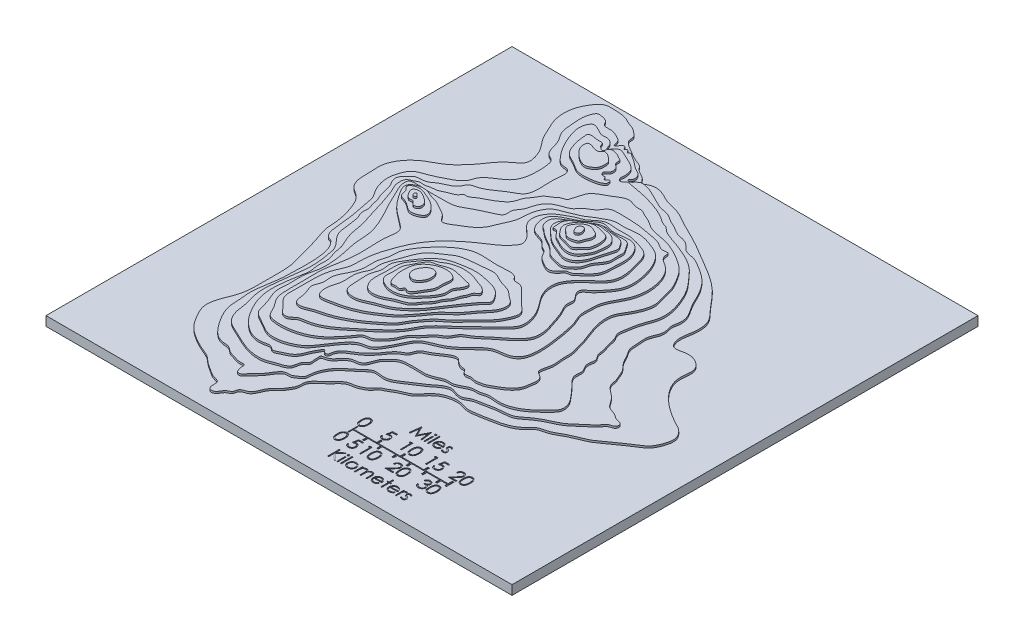
SolidWorks part; units mm, degrees
ref_plane "Front Plane" through (0, 0, 0) normal (0, 0, 1) x (1, 0, 0)
ref_plane "Top Plane" through (0, 0, 0) normal (0, 1, 0) x (1, 0, 0)
ref_plane "Right Plane" through (0, 0, 0) normal (1, 0, 0) x (0, 0, -1)
sketch "Sketch1" plane through (0, 0, 0) normal (0, 1, 0) x (1, 0, 0)
  line L1 (-63.5, -63.5) -> (63.5, -63.5)
  line L2 (-63.5, -63.5) -> (-63.5, 63.5)
  line L3 (-63.5, 63.5) -> (63.5, 63.5)
  line L4 (63.5, -63.5) -> (63.5, 63.5)
  line L5 (-63.5, -63.5) -> (63.5, 63.5) construction
  line L6 (-63.5, 63.5) -> (63.5, -63.5) construction
  point P0 (0, 0)
  dimension "D1" = 127
  dimension "D2" = 127
extrude "Table" add sketch "Sketch1" along normal blind 2.54
sketch "Master" plane through (0, 2.54, 0) normal (0, 1, 0) x (1, 0, 0)
  line L0 (28.8333, 259.5) -> (398.1667, 259.5) construction
  line L1 (6.35, -46.8068) -> (29.21, -46.8068) construction
  line L2 (5.0423, -48.3753) -> (31.4087, -48.3753)
  line L3 (5.0423, -48.3753) -> (5.0423, -48.6293)
  line L4 (5.0423, -48.6293) -> (31.4087, -48.6293)
  line L5 (31.4087, -48.3753) -> (31.4087, -48.6293)
  line L6 (30.9502, -47.2308) -> (31.4087, -47.2308)
  line L7 (30.9502, -47.2308) -> (30.9502, -49.2894)
  line L8 (30.9502, -49.2894) -> (31.4087, -49.2894)
  line L9 (31.4087, -47.2308) -> (31.4087, -49.2894)
  line L10 (28.8818, -48.6293) -> (29.3366, -48.6293)
  line L11 (28.8818, -48.6293) -> (28.8818, -49.7264)
  line L12 (28.8818, -49.7264) -> (29.3366, -49.7264)
  line L13 (29.3366, -48.6293) -> (29.3366, -49.7264)
  line L14 (24.9746, -48.6293) -> (25.4571, -48.6293)
  line L15 (24.9746, -48.6293) -> (24.9746, -49.7264)
  line L16 (24.9746, -49.7264) -> (25.4571, -49.7264)
  line L17 (25.4571, -48.6293) -> (25.4571, -49.7264)
  line L18 (24.3147, -47.2308) -> (24.7619, -47.2308)
  line L19 (24.3147, -47.2308) -> (24.3147, -48.3753)
  line L20 (24.3147, -48.3753) -> (24.7619, -48.3753)
  line L21 (24.7619, -47.2308) -> (24.7619, -48.3753)
  line L22 (20.8599, -48.6293) -> (21.3202, -48.6293)
  line L23 (20.8599, -48.6293) -> (20.8599, -49.7264)
  line L24 (20.8599, -49.7264) -> (21.3202, -49.7264)
  line L25 (21.3202, -48.6293) -> (21.3202, -49.7264)
  line L26 (16.9577, -48.6293) -> (17.4289, -48.6293)
  line L27 (16.9577, -48.6293) -> (16.9577, -49.7264)
  line L28 (16.9577, -49.7264) -> (17.4289, -49.7264)
  line L29 (17.4289, -48.6293) -> (17.4289, -49.7264)
  line L30 (17.8871, -47.2308) -> (18.3452, -47.2308)
  line L31 (17.8871, -47.2308) -> (17.8871, -48.3753)
  line L32 (17.8871, -48.3753) -> (18.3452, -48.3753)
  line L33 (18.3452, -47.2308) -> (18.3452, -48.3753)
  line L34 (12.843, -48.6293) -> (13.292, -48.6293)
  line L35 (12.843, -48.6293) -> (12.843, -49.7264)
  line L36 (12.843, -49.7264) -> (13.292, -49.7264)
  line L37 (13.292, -48.6293) -> (13.292, -49.7264)
  line L38 (11.476, -47.2308) -> (11.9251, -47.2308)
  line L39 (11.476, -47.2308) -> (11.476, -48.3753)
  line L40 (11.476, -48.3753) -> (11.9251, -48.3753)
  line L41 (11.9251, -47.2308) -> (11.9251, -48.3753)
  line L42 (8.9486, -48.6293) -> (9.3972, -48.6293)
  line L43 (8.9486, -48.6293) -> (8.9486, -49.7264)
  line L44 (8.9486, -49.7264) -> (9.3972, -49.7264)
  line L45 (9.3972, -48.6293) -> (9.3972, -49.7264)
  line L46 (5.0423, -48.3753) -> (5.2588, -48.3753)
  line L47 (5.0423, -48.3753) -> (5.0423, -47.2308)
  line L48 (5.0423, -47.2308) -> (5.2588, -47.2308)
  line L49 (5.2588, -48.3753) -> (5.2588, -47.2308)
  line L50 (5.0423, -48.6293) -> (5.2588, -48.6293)
  line L51 (5.0423, -48.6293) -> (5.0423, -49.7264)
  line L52 (5.0423, -49.7264) -> (5.2588, -49.7264)
  line L53 (5.2588, -48.6293) -> (5.2588, -49.7264)
  line L54 (13.292, -41.6326) -> (23.4459, -41.6326) construction
  line L55 (23.4459, -41.6326) -> (23.4459, -46.8068) construction
  line L56 (23.4459, -46.8068) -> (23.4459, -48.3753) construction
  line L57 (6.35, -53.34) -> (26.67, -53.3257) construction
  line L58 (26.67, -53.3257) -> (26.67, -58.2919) construction
  line L59 (26.67, -58.2919) -> (7.62, -58.2919) construction
  line L60 (22.5347, -48.6293) -> (22.5347, -53.3286) construction
  spline S0 degree 3 number of poles 136 (-30.2533, 61.4196) -> (-30.2533, 61.4196)
  spline S1 degree 3 number of poles 164 (-35.5805, 57.4705) -> (-35.5805, 57.4705)
  spline S2 degree 3 number of poles 140 (-33.4819, 53.3721) -> (-33.4819, 53.3721)
  spline S3 degree 3 poles (-26.25, 51.1954) (-27.5323, 51.0076) (-28.575, 51.2687) (-30.6963, 51.4713) (-30.3649, 49.7693) (-30.3171, 48.3479) (-29.7101, 46.1998) (-28.5554, 43.5195) (-25.7194, 42.6435) (-23.1147, 40.5022) (-19.8391, 40.7603) (-17.3898, 41.1982) (-16.1906, 42.0292) (-16.2154, 42.7209) (-16.5264, 43.7067) (-17.4633, 42.1742) (-17.7597, 43.0865) (-18.0522, 43.4981) (-18.5561, 43.2978) (-19.0607, 43.5182) (-19.4986, 43.9714) (-19.2974, 44.55) (-18.9531, 44.9092) (-18.1361, 45.4421) (-18.3728, 46.8498) (-19.1699, 47.4741) (-19.6627, 47.8231) (-19.9632, 48.4852) (-19.6996, 49.4175) (-20.808, 49.7315) (-21.5934, 50.4228) (-22.6702, 50.6189) (-23.6199, 50.7926) (-24.2289, 50.2669) (-24.2639, 49.7102) (-24.6735, 49.0969) (-25.3781, 49.6079) (-26.0745, 50.0605) (-26.25, 51.1954) (-27.5323, 51.0076) (-28.575, 51.2687) knots -0.055235 -0.036483 -0.009705 0 0.043313 0.079211 0.100968 0.139976 0.183739 0.251086 0.32677 0.373438 0.477244 0.527201 0.552559 0.56082 0.575588 0.601018 0.616226 0.621801 0.633895 0.645623 0.65892 0.671786 0.682091 0.693251 0.736089 0.74848 0.76343 0.776187 0.796472 0.816749 0.840821 0.869342 0.889931 0.902722 0.918216 0.92825 0.944765 0.963517 0.990295 1 1.043313 1.079211 1.100968 only from (-26.9845, 51.0961) to (-26.9845, 51.0961)
  spline S4 degree 3 poles (-23.8681, 48.8647) (-24.2474, 47.8693) (-25.5025, 47.9527) (-26.4325, 48.42) (-27.9645, 48.7604) (-28.1074, 47.5041) (-27.9803, 46.5295) (-27.0766, 45.2128) (-25.8718, 44.0711) (-24.3589, 43.1337) (-22.9884, 42.6671) (-21.9283, 43.1795) (-21.159, 43.6249) (-20.541, 44.453) (-20.4464, 45.6175) (-20.4924, 47.0156) (-21.4827, 47.7844) (-22.2461, 48.44) (-22.9571, 48.7456) (-23.8681, 48.8647) (-24.2474, 47.8693) (-25.5025, 47.9527) knots -0.11115 -0.071618 -0.042286 0 0.043927 0.10396 0.164652 0.19766 0.251336 0.30265 0.41016 0.476707 0.549357 0.592242 0.632479 0.671219 0.727506 0.790535 0.850099 0.88885 0.928382 0.957714 1 1.043927 1.10396 1.164652 only from (-24.3519, 48.0739) to (-24.3519, 48.0739)
  spline S5 degree 3 number of poles 122 (-30.9511, 20.7382) -> (-30.9511, 20.7382)
  spline S6 degree 3 number of poles 74 (-43.2944, 15.0999) -> (-43.2944, 15.0999)
  spline S7 degree 3 number of poles 71 (-42.0642, 13.5601) -> (-42.0642, 13.5601)
  spline S8 degree 3 poles (-37.2309, 13.4684) (-39.7598, 14.4094) (-41.8012, 12.5919) (-40.0411, 11.562) (-40.3673, 9.5716) (-38.3217, 9.1819) (-36.8913, 8.3368) (-35.4914, 7.0475) (-33.5219, 7.1297) (-31.3018, 8.3047) (-32.6117, 10.8125) (-34.4662, 12.268) (-37.2309, 13.4684) (-39.7598, 14.4094) (-41.8012, 12.5919) knots -0.372051 -0.251341 -0.150038 0 0.045939 0.106045 0.178712 0.24492 0.317628 0.392158 0.462121 0.554328 0.627949 0.748659 0.849962 1 1.045939 1.106045 1.178712 only from (-40.5839, 13.5601) to (-40.5839, 13.5601)
  spline S9 degree 3 poles (-38.3357, 12.8672) (-39.6445, 12.3096) (-39.0336, 10.8418) (-38.4225, 10.0241) (-37.5228, 9.4087) (-36.5774, 9.8206) (-36.0786, 8.9472) (-35.2767, 8.3867) (-34.0754, 9.0145) (-34.2642, 10.7241) (-35.6661, 11.7101) (-37.0747, 12.5877) (-38.3357, 12.8672) (-39.6445, 12.3096) (-39.0336, 10.8418) knots -0.271011 -0.157905 -0.067699 0 0.085169 0.196973 0.233096 0.303903 0.367091 0.416389 0.50008 0.582128 0.728989 0.842095 0.932301 1 1.085169 1.196973 1.233096 only from (-39.3198, 12.2522) to (-39.3198, 12.2522)
  spline S10 degree 3 poles (-36.8664, 11.0994) (-37.5581, 11.5528) (-37.7525, 10.6942) (-37.2936, 10.1676) (-36.4158, 10.4147) (-36.8664, 11.0994) (-37.5581, 11.5528) (-37.7525, 10.6942) knots -0.603978 -0.413436 -0.204471 0 0.186531 0.396022 0.586564 0.795529 1 1.186531 1.396022 1.586564 only from (-37.4901, 11.3326) to (-37.4901, 11.3326)
  spline S11 degree 3 poles (-23.9334, 4.8467) (-27.2505, -0.4812) (-28.6869, -4.2735) (-29.7731, -7.7232) (-30.1234, -11.0677) (-29.9909, -14.2889) (-31.7625, -17.4021) (-32.3429, -21.6508) (-32.0249, -25.9262) (-32.4862, -30.4488) (-29.6943, -32.4077) (-28.215, -34.7053) (-26.318, -34.3281) (-25.3369, -33.0383) (-21.4773, -32.8017) (-18.0048, -30.7633) (-14.6997, -27.8844) (-12.4422, -26.2098) (-9.9147, -23.769) (-7.4834, -21.2962) (-6.1591, -17.8977) (-3.5706, -15.4967) (-0.4157, -12.821) (2.558, -9.769) (5.239, -7.2705) (7.4409, -4.9518) (7.1023, -1.5577) (5.563, 1.8291) (3.1631, 4.4263) (1.8419, 7.42) (1.7691, 10.6676) (3.8571, 13.5049) (6.5156, 15.8503) (9.0566, 18.0907) (9.496, 21.8973) (8.4093, 25.1992) (7.5316, 29.2721) (3.9776, 30.4642) (0.7535, 31.4411) (-2.6245, 30.9777) (-5.6924, 31.6865) (-7.663, 30.1804) (-9.0257, 28.9099) (-10.9716, 28.3898) (-12.5961, 27.4549) (-14.8985, 26.1971) (-16.8606, 23.8197) (-16.5698, 20.1723) (-14.3925, 18.4817) (-12.6909, 16.8957) (-11.6832, 14.8883) (-13.1538, 12.7873) (-14.8596, 11.2091) (-19.2804, 8.4043) (-23.9334, 4.8467) (-27.2505, -0.4812) (-28.6869, -4.2735) knots -0.095833 -0.083437 -0.026803 0 0.020178 0.040909 0.060109 0.076353 0.093499 0.118392 0.146161 0.167538 0.186834 0.200193 0.207991 0.214723 0.226072 0.268211 0.280201 0.299385 0.315011 0.339013 0.356394 0.374693 0.396921 0.425912 0.445279 0.459181 0.476591 0.497453 0.521427 0.534642 0.551523 0.572891 0.59038 0.61198 0.626271 0.651043 0.671492 0.689587 0.708665 0.728002 0.746151 0.757247 0.767465 0.77706 0.790141 0.798693 0.821061 0.836963 0.853919 0.864437 0.87709 0.886061 0.904167 0.916563 0.973197 1 1.020178 1.040909 1.060109 only from (-27.2975, -0.892) to (-27.2975, -0.892)
  spline S12 degree 3 poles (-3.5992, 23.4735) (-4.5186, 23.6615) (-5.1567, 22.82) (-4.8062, 21.8789) (-4.212, 20.7677) (-2.9576, 21.5278) (-3.159, 22.637) (-3.5992, 23.4735) (-4.5186, 23.6615) (-5.1567, 22.82) knots -0.409048 -0.219639 -0.091473 0 0.157501 0.268887 0.4616 0.590952 0.780361 0.908527 1 1.157501 1.268887 1.4616 only from (-4.3352, 23.5333) to (-4.3352, 23.5333)
  spline S13 degree 3 poles (-5.0025, 24.9942) (-5.9493, 24.1236) (-6.6241, 23.2412) (-7.2151, 22.1412) (-6.5495, 21.0892) (-5.686, 20.3677) (-4.6624, 19.3564) (-3.2383, 19.5617) (-1.7804, 19.9289) (-1.5567, 21.2995) (-0.8849, 22.3222) (-0.8629, 23.9745) (-2.3602, 24.6595) (-3.668, 25.2889) (-5.0025, 24.9942) (-5.9493, 24.1236) (-6.6241, 23.2412) knots -0.21033 -0.132104 -0.060152 0 0.078479 0.130245 0.191237 0.261533 0.326885 0.415373 0.488039 0.552112 0.623149 0.697462 0.78967 0.867896 0.939848 1 1.078479 1.130245 1.191237 only from (-5.842, 24.1863) to (-5.842, 24.1863)
  spline S14 degree 3 poles (-7.6584, 24.4387) (-8.4318, 21.9288) (-7.4007, 20.4703) (-6.0931, 18.9396) (-4.0777, 18.8763) (-1.6018, 17.5951) (-0.615, 19.6344) (0.5688, 20.3607) (0.7978, 21.4249) (0.9993, 22.7061) (0.804, 24.1301) (0.3207, 25.548) (-1.0918, 25.9806) (-2.394, 26.2608) (-3.7157, 26.6582) (-5.9223, 26.1198) (-7.6584, 24.4387) (-8.4318, 21.9288) (-7.4007, 20.4703) knots -0.24476 -0.197198 -0.050701 0 0.077353 0.130465 0.215663 0.293607 0.390065 0.40941 0.444231 0.501346 0.555113 0.603632 0.654427 0.705275 0.75524 0.802802 0.949299 1 1.077353 1.130465 1.215663 only from (-8.1859, 22.1944) to (-8.1859, 22.1944)
  spline S15 degree 3 poles (-10.1061, 24.5421) (-9.6828, 22.0738) (-9.6633, 20.565) (-8.5766, 20.9078) (-7.8435, 19.9578) (-7.0884, 18.9316) (-5.7157, 18.3576) (-4.3733, 17.5654) (-2.8842, 17.1181) (-1.3527, 17.0758) (0.0761, 17.7051) (1.0052, 19.1468) (1.9159, 20.6171) (2.0619, 22.5896) (2.3472, 24.4573) (1.3345, 26.1641) (-0.2456, 27.1341) (-2.1269, 27.2783) (-4.1063, 27.7143) (-6.6386, 26.1744) (-10.1061, 24.5421) (-9.6828, 22.0738) (-9.6633, 20.565) knots -0.257336 -0.200144 -0.058266 0 0.022229 0.039464 0.075298 0.11168 0.150258 0.198379 0.246045 0.281136 0.328188 0.371132 0.425814 0.473189 0.539096 0.580718 0.635224 0.6902 0.742664 0.799856 0.941734 1 1.022229 1.039464 1.075298 only from (-9.6861, 21.4908) to (-9.6861, 21.4908)
  spline S16 degree 3 poles (-5.5833, 30.8221) (-8.4506, 27.5184) (-11.804, 26.448) (-14.7865, 24.3519) (-14.5145, 21.3936) (-13.0906, 18.4) (-9.596, 18.3091) (-8.3176, 16.2431) (-6.602, 15.6709) (-6.0823, 14.0742) (-4.6416, 12.9569) (-3.3424, 12.1987) (-1.6196, 11.491) (-0.0802, 12.5181) (0.751, 13.9964) (2.1332, 13.8955) (3.3529, 15.1297) (4.8703, 16.2726) (6.3327, 18.323) (6.3164, 21.5279) (6.7943, 24.9096) (5.5649, 28.0523) (3.6972, 29.8357) (1.4371, 29.9166) (-0.6189, 29.5235) (-2.7813, 29.3597) (-5.5833, 30.8221) (-8.4506, 27.5184) (-11.804, 26.448) knots -0.137227 -0.101474 -0.063507 0 0.073184 0.119652 0.156586 0.2072 0.266128 0.301348 0.31688 0.349921 0.37431 0.404087 0.424345 0.460124 0.481825 0.500715 0.519113 0.562576 0.595097 0.636164 0.71432 0.758711 0.795704 0.832283 0.862773 0.898526 0.936493 1 1.073184 1.119652 1.156586 only from (-8.3475, 28.0871) to (-8.3475, 28.0871)
  spline S17 degree 3 poles (-5.9253, 28.3984) (-8.1248, 27.0759) (-10.3741, 25.531) (-13.1073, 24.0285) (-12.9844, 21.9195) (-12.3925, 20.6061) (-11.3235, 20.08) (-10.1379, 18.8753) (-8.591, 18.0796) (-6.9458, 17.1597) (-5.814, 16.2084) (-4.6774, 14.8081) (-2.6051, 14.4874) (-0.3701, 13.6176) (1.3522, 15.0837) (2.7133, 16.3973) (2.8299, 18.4203) (4.0801, 19.9123) (5.2136, 21.696) (4.813, 23.6481) (5.253, 25.5906) (3.9812, 26.9496) (3.1995, 28.6457) (1.029, 28.6942) (-1.2258, 28.4859) (-3.6968, 29.3506) (-5.9253, 28.3984) (-8.1248, 27.0759) (-10.3741, 25.531) knots -0.136528 -0.079066 -0.041169 0 0.070746 0.125105 0.160389 0.181931 0.206541 0.226852 0.280432 0.306669 0.336782 0.366908 0.407807 0.456199 0.493565 0.529884 0.563872 0.604319 0.64215 0.680916 0.716876 0.749415 0.784172 0.816555 0.863472 0.920934 0.958831 1 1.070746 1.125105 1.160389 only from (-7.6731, 27.33) to (-7.6731, 27.33)
  spline S18 degree 3 poles (-1.8925, 28.0021) (-4.5391, 28.8222) (-7.1687, 26.2379) (-10.4064, 25.0405) (-11.2039, 22.0411) (-10.0759, 20.3671) (-8.7236, 19.3717) (-7.7105, 18.3578) (-6.4365, 17.4804) (-4.8399, 16.8851) (-3.195, 16.1816) (-1.2946, 15.4423) (1.1393, 16.4334) (2.3532, 18.8937) (2.9595, 21.4234) (3.453, 23.4055) (4.069, 25.1346) (3.1775, 26.3099) (2.2374, 27.6948) (0.1401, 27.8196) (-1.8925, 28.0021) (-4.5391, 28.8222) (-7.1687, 26.2379) knots -0.15109 -0.099752 -0.049404 0 0.082075 0.186335 0.230064 0.280834 0.317468 0.350229 0.382045 0.42642 0.470233 0.510233 0.566735 0.636171 0.696523 0.750952 0.785281 0.815976 0.84891 0.900248 0.950596 1 1.082075 1.186335 1.230064 only from (-4.0004, 28.3876) to (-4.0004, 28.3876)
  spline S19 degree 3 poles (-23.8345, 0.3158) (-25.3778, -1.8488) (-26.6154, -4.2575) (-26.326, -6.9786) (-27.5784, -9.5703) (-27.056, -12.8391) (-28.1605, -16.1674) (-30.091, -19.1328) (-29.1829, -22.0602) (-30.7465, -24.2378) (-29.4307, -26.363) (-29.1306, -28.24) (-28.9701, -30.169) (-27.2724, -30.7711) (-25.754, -30.2027) (-24.3229, -29.5544) (-20.9026, -28.8556) (-17.019, -27.0911) (-13.5195, -24.64) (-11.4477, -22.9293) (-9.8252, -21.6708) (-8.7491, -19.2939) (-7.2578, -17.3477) (-5.5414, -15.083) (-3.5892, -13.9046) (-1.6453, -11.9096) (0.3419, -9.6845) (2.8583, -7.4669) (4.1576, -4.9101) (5.1732, -2.4307) (2.7123, -0.036) (0.4638, 1.9105) (-1.7855, 4.6773) (-4.0235, 4.2918) (-5.1261, 6.2188) (-8.5049, 5.7878) (-11.9024, 5.8612) (-15.7906, 6.1975) (-19.1648, 4.7613) (-21.7097, 2.6149) (-23.8345, 0.3158) (-25.3778, -1.8488) (-26.6154, -4.2575) knots -0.084142 -0.050862 -0.027201 0 0.021177 0.043662 0.07123 0.095598 0.130022 0.164545 0.184558 0.206863 0.22675 0.244797 0.26034 0.273406 0.286144 0.303435 0.31577 0.379959 0.416523 0.430701 0.452722 0.470582 0.499878 0.518968 0.546579 0.560281 0.593891 0.62767 0.648146 0.673647 0.688713 0.733541 0.76063 0.775096 0.785861 0.813394 0.853435 0.883354 0.915858 0.949138 0.972799 1 1.021177 1.043662 1.07123 only from (-25.4463, -2.0902) to (-25.4463, -2.0902)
  spline S20 degree 3 poles (-22.3851, -1.2204) (-23.6089, -4.7138) (-24.7375, -7.7984) (-25.6964, -10.4861) (-25.173, -12.7478) (-26.077, -14.4105) (-26.8883, -16.5852) (-26.1464, -19.7926) (-27.6538, -22.7136) (-26.9717, -26.5677) (-22.2852, -25.6782) (-19.1327, -24.9636) (-15.7686, -23.2655) (-13.8602, -21.9965) (-11.4322, -20.3858) (-9.4915, -18.1461) (-7.702, -15.773) (-6.0003, -13.2223) (-3.3039, -11.4355) (-1.767, -8.781) (-0.0378, -6.7983) (1.598, -4.8939) (1.9692, -1.8317) (-0.3612, -0.5492) (-1.8312, 1.0604) (-3.9732, 1.486) (-5.7246, 2.207) (-7.7184, 3.4187) (-10.9238, 2.8571) (-14.1265, 2.7572) (-17.1989, 2.1507) (-19.3294, 0.3587) (-22.3851, -1.2204) (-23.6089, -4.7138) (-24.7375, -7.7984) knots -0.109207 -0.081403 -0.043528 0 0.033716 0.066976 0.091835 0.105385 0.127965 0.167529 0.205743 0.239303 0.263976 0.340192 0.35548 0.387277 0.416026 0.451113 0.484159 0.514481 0.551334 0.588207 0.614145 0.637834 0.672241 0.695732 0.719062 0.743112 0.764999 0.78213 0.818138 0.865707 0.890793 0.918597 0.956472 1 1.033716 1.066976 1.091835 only from (-23.7029, -4.9519) to (-23.7029, -4.9519)
  spline S21 degree 3 poles (-19.969, -2.8831) (-21.5644, -5.338) (-22.9763, -7.5241) (-24.0304, -9.5392) (-23.1815, -11.9533) (-24.5912, -14.6403) (-23.9583, -17.7697) (-24.2704, -21.6266) (-20.232, -22.7579) (-17.2446, -20.8426) (-13.742, -19.9046) (-11.1401, -18.0415) (-8.8189, -15.8127) (-6.889, -12.8263) (-5.1872, -10.167) (-3.4405, -7.7777) (-2.3184, -6.1198) (-0.6259, -4.8143) (-1.7343, -2.7736) (-3.3876, -0.9475) (-6.7053, -0.0906) (-10.1483, 0.6) (-13.7307, 0.0313) (-17.147, -0.6456) (-19.969, -2.8831) (-21.5644, -5.338) (-22.9763, -7.5241) knots -0.145751 -0.098686 -0.051054 0 0.022986 0.059325 0.088777 0.12268 0.177253 0.225003 0.259033 0.325274 0.368401 0.409794 0.457432 0.502557 0.557908 0.590314 0.625136 0.645651 0.667179 0.70738 0.750828 0.805057 0.854249 0.901314 0.948946 1 1.022986 1.059325 1.088777 only from (-21.9212, -5.8913) to (-21.9212, -5.8913)
  spline S22 degree 3 poles (-21.543, -7.3765) (-22.1417, -9.6071) (-21.8732, -12.5397) (-22.4503, -15.9498) (-20.5962, -19.645) (-17.0921, -19.3101) (-15.18, -18.1283) (-13.3949, -17.342) (-10.9412, -16.8254) (-9.8747, -14.365) (-8.1975, -12.9402) (-7.8146, -11.1054) (-6.3802, -9.8571) (-6.1724, -8.0716) (-5.2209, -6.8226) (-5.162, -5.3811) (-3.4448, -4.7686) (-4.9574, -2.9044) (-6.5738, -2.6289) (-8.6501, -1.574) (-11.0657, -1.1078) (-13.6383, -1.2872) (-15.2807, -1.856) (-16.3157, -2.4686) (-17.0212, -3.028) (-18.2026, -3.2405) (-19.367, -4.4232) (-20.3315, -5.9261) (-21.543, -7.3765) (-22.1417, -9.6071) (-21.8732, -12.5397) knots -0.098505 -0.059144 -0.028901 0 0.060264 0.125359 0.183171 0.247549 0.280315 0.303979 0.351212 0.403731 0.435022 0.464865 0.498171 0.53012 0.555092 0.579931 0.599117 0.628879 0.664534 0.693043 0.749348 0.793109 0.828256 0.840078 0.856842 0.875181 0.901495 0.940856 0.971099 1 1.060264 1.125359 1.183171 only from (-21.9212, -9.0243) to (-21.9212, -9.0243)
  spline S23 degree 3 poles (-18.8301, -5.8794) (-19.5639, -7.5832) (-20.7029, -9.4144) (-20.2715, -11.745) (-21.0482, -14.6324) (-18.0843, -16.4709) (-15.3456, -16.8228) (-12.5067, -15.6723) (-10.5788, -13.6333) (-8.9986, -11.6604) (-8.1501, -9.7258) (-8.6055, -8.0531) (-7.6385, -6.7302) (-7.0311, -5.7617) (-6.8888, -4.4537) (-8.2979, -4.2644) (-9.5579, -3.9352) (-11.1912, -3.4839) (-13.1447, -3.1043) (-14.8657, -3.7326) (-16.2516, -4.3467) (-17.6329, -4.3515) (-18.8301, -5.8794) (-19.5639, -7.5832) (-20.7029, -9.4144) knots -0.124501 -0.094947 -0.05967 0 0.040283 0.083536 0.162349 0.219434 0.298327 0.351474 0.426619 0.491362 0.529264 0.56918 0.602597 0.636681 0.652688 0.6821 0.713199 0.751456 0.798623 0.849688 0.875499 0.905053 0.94033 1 1.040283 1.083536 1.162349 only from (-19.7591, -7.8341) to (-19.7591, -7.8341)
  spline S24 degree 3 poles (-18.6015, -7.5493) (-19.069, -9.7532) (-19.0414, -11.9743) (-18.5378, -13.9006) (-17.6731, -15.7308) (-16.2597, -15.2251) (-14.9179, -15.8602) (-14.5847, -14.3083) (-13.0251, -15.6718) (-11.5725, -12.5974) (-10.054, -10.7853) (-10.4501, -8.2494) (-9.6361, -5.9511) (-12.1582, -4.5556) (-14.6509, -4.7125) (-17.0786, -5.8898) (-18.6015, -7.5493) (-19.069, -9.7532) (-19.0414, -11.9743) knots -0.200371 -0.123546 -0.050648 0 0.083979 0.150836 0.198715 0.237381 0.275413 0.305846 0.327748 0.416128 0.513821 0.565393 0.648899 0.701087 0.799629 0.876454 0.949352 1 1.083979 1.150836 1.198715 only from (-18.9484, -9.4069) to (-18.9484, -9.4069)
  spline S25 degree 3 poles (-16.3723, -7.919) (-17.2462, -9.3555) (-17.0083, -11.1431) (-15.9419, -11.8535) (-14.9234, -12.2808) (-13.626, -11.3964) (-12.8066, -10.0645) (-12.8349, -8.4881) (-13.3295, -6.9979) (-15.1945, -6.7056) (-16.3723, -7.919) (-17.2462, -9.3555) (-17.0083, -11.1431) knots -0.333815 -0.214553 -0.121861 0 0.130477 0.194722 0.260834 0.342461 0.488641 0.568434 0.666185 0.785447 0.878139 1 1.130477 1.194722 1.260834 only from (-17.0311, -9.4069) to (-17.0311, -9.4069)
  text T0 "0"
  text T1 "0"
  text T2 "5"
  text T3 "5"
  text T4 "10"
  text T5 "15"
  text T6 "20"
  text T7 "10"
  text T8 "20"
  text T9 "30"
  text T10 "Miles"
  text T11 "Kilometers"
  dimension "D1" = 0.254
sketch "Sketch3" plane through (0, 2.54, 0) normal (0, 1, 0) x (1, 0, 0)
  spline S0 degree 3 number of poles 136 (-30.2533, 61.4196) -> (-30.2533, 61.4196) construction
  spline S1 degree 3 number of poles 136 (-30.2533, 61.4196) -> (-30.2533, 61.4196)
extrude "Ground" add sketch "Sketch3" along normal blind 0.508
sketch "Sketch4" plane through (0, 3.048, 0) normal (0, 1, 0) x (1, 0, 0)
  spline S0 degree 3 number of poles 164 (-35.5805, 57.4705) -> (-35.5805, 57.4705) construction
  spline S1 degree 3 number of poles 164 (-35.5805, 57.4705) -> (-35.5805, 57.4705)
extrude "1000" add sketch "Sketch4" along normal blind 0.508
sketch "Sketch5" plane through (0, 3.556, 0) normal (0, 1, 0) x (1, 0, 0)
  spline S0 degree 3 number of poles 140 (-33.4819, 53.3721) -> (-33.4819, 53.3721) construction
  spline S1 degree 3 number of poles 140 (-33.4819, 53.3721) -> (-33.4819, 53.3721)
extrude "2000" add sketch "Sketch5" along normal blind 0.508
sketch "Sketch6" plane through (0, 4.064, 0) normal (0, 1, 0) x (1, 0, 0)
  spline S0 degree 3 number of poles 122 (-30.9511, 20.7382) -> (-30.9511, 20.7382) construction
  spline S1 degree 3 poles (-26.25, 51.1954) (-27.5323, 51.0076) (-28.575, 51.2687) (-30.6963, 51.4713) (-30.3649, 49.7693) (-30.3171, 48.3479) (-29.7101, 46.1998) (-28.5554, 43.5195) (-25.7194, 42.6435) (-23.1147, 40.5022) (-19.8391, 40.7603) (-17.3898, 41.1982) (-16.1906, 42.0292) (-16.2154, 42.7209) (-16.5264, 43.7067) (-17.4633, 42.1742) (-17.7597, 43.0865) (-18.0522, 43.4981) (-18.5561, 43.2978) (-19.0607, 43.5182) (-19.4986, 43.9714) (-19.2974, 44.55) (-18.9531, 44.9092) (-18.1361, 45.4421) (-18.3728, 46.8498) (-19.1699, 47.4741) (-19.6627, 47.8231) (-19.9632, 48.4852) (-19.6996, 49.4175) (-20.808, 49.7315) (-21.5934, 50.4228) (-22.6702, 50.6189) (-23.6199, 50.7926) (-24.2289, 50.2669) (-24.2639, 49.7102) (-24.6735, 49.0969) (-25.3781, 49.6079) (-26.0745, 50.0605) (-26.25, 51.1954) (-27.5323, 51.0076) (-28.575, 51.2687) knots -0.055235 -0.036483 -0.009705 0 0.043313 0.079211 0.100968 0.139976 0.183739 0.251086 0.32677 0.373438 0.477244 0.527201 0.552559 0.56082 0.575588 0.601018 0.616226 0.621801 0.633895 0.645623 0.65892 0.671786 0.682091 0.693251 0.736089 0.74848 0.76343 0.776187 0.796472 0.816749 0.840821 0.869342 0.889931 0.902722 0.918216 0.92825 0.944765 0.963517 0.990295 1 1.043313 1.079211 1.100968 only from (-26.9845, 51.0961) to (-26.9845, 51.0961) construction
  spline S2 degree 3 number of poles 122 (-30.9511, 20.7382) -> (-30.9511, 20.7382)
  spline S3 degree 3 poles (-26.25, 51.1954) (-27.5323, 51.0076) (-28.575, 51.2687) (-30.6963, 51.4713) (-30.3649, 49.7693) (-30.3171, 48.3479) (-29.7101, 46.1998) (-28.5554, 43.5195) (-25.7194, 42.6435) (-23.1147, 40.5022) (-19.8391, 40.7603) (-17.3898, 41.1982) (-16.1906, 42.0292) (-16.2154, 42.7209) (-16.5264, 43.7067) (-17.4633, 42.1742) (-17.7597, 43.0865) (-18.0522, 43.4981) (-18.5561, 43.2978) (-19.0607, 43.5182) (-19.4986, 43.9714) (-19.2974, 44.55) (-18.9531, 44.9092) (-18.1361, 45.4421) (-18.3728, 46.8498) (-19.1699, 47.4741) (-19.6627, 47.8231) (-19.9632, 48.4852) (-19.6996, 49.4175) (-20.808, 49.7315) (-21.5934, 50.4228) (-22.6702, 50.6189) (-23.6199, 50.7926) (-24.2289, 50.2669) (-24.2639, 49.7102) (-24.6735, 49.0969) (-25.3781, 49.6079) (-26.0745, 50.0605) (-26.25, 51.1954) (-27.5323, 51.0076) (-28.575, 51.2687) knots -0.055235 -0.036483 -0.009705 0 0.043313 0.079211 0.100968 0.139976 0.183739 0.251086 0.32677 0.373438 0.477244 0.527201 0.552559 0.56082 0.575588 0.601018 0.616226 0.621801 0.633895 0.645623 0.65892 0.671786 0.682091 0.693251 0.736089 0.74848 0.76343 0.776187 0.796472 0.816749 0.840821 0.869342 0.889931 0.902722 0.918216 0.92825 0.944765 0.963517 0.990295 1 1.043313 1.079211 1.100968 only from (-26.9845, 51.0961) to (-26.9845, 51.0961)
extrude "3000" add sketch "Sketch6" along normal blind 0.508
sketch "Sketch7" plane through (0, 4.572, 0) normal (0, 1, 0) x (1, 0, 0)
  spline S0 degree 3 number of poles 74 (-43.2944, 15.0999) -> (-43.2944, 15.0999) construction
  spline S1 degree 3 poles (-23.8681, 48.8647) (-24.2474, 47.8693) (-25.5025, 47.9527) (-26.4325, 48.42) (-27.9645, 48.7604) (-28.1074, 47.5041) (-27.9803, 46.5295) (-27.0766, 45.2128) (-25.8718, 44.0711) (-24.3589, 43.1337) (-22.9884, 42.6671) (-21.9283, 43.1795) (-21.159, 43.6249) (-20.541, 44.453) (-20.4464, 45.6175) (-20.4924, 47.0156) (-21.4827, 47.7844) (-22.2461, 48.44) (-22.9571, 48.7456) (-23.8681, 48.8647) (-24.2474, 47.8693) (-25.5025, 47.9527) knots -0.11115 -0.071618 -0.042286 0 0.043927 0.10396 0.164652 0.19766 0.251336 0.30265 0.41016 0.476707 0.549357 0.592242 0.632479 0.671219 0.727506 0.790535 0.850099 0.88885 0.928382 0.957714 1 1.043927 1.10396 1.164652 only from (-24.3519, 48.0739) to (-24.3519, 48.0739) construction
  spline S2 degree 3 number of poles 74 (-43.2944, 15.0999) -> (-43.2944, 15.0999)
  spline S3 degree 3 poles (-23.8681, 48.8647) (-24.2474, 47.8693) (-25.5025, 47.9527) (-26.4325, 48.42) (-27.9645, 48.7604) (-28.1074, 47.5041) (-27.9803, 46.5295) (-27.0766, 45.2128) (-25.8718, 44.0711) (-24.3589, 43.1337) (-22.9884, 42.6671) (-21.9283, 43.1795) (-21.159, 43.6249) (-20.541, 44.453) (-20.4464, 45.6175) (-20.4924, 47.0156) (-21.4827, 47.7844) (-22.2461, 48.44) (-22.9571, 48.7456) (-23.8681, 48.8647) (-24.2474, 47.8693) (-25.5025, 47.9527) knots -0.11115 -0.071618 -0.042286 0 0.043927 0.10396 0.164652 0.19766 0.251336 0.30265 0.41016 0.476707 0.549357 0.592242 0.632479 0.671219 0.727506 0.790535 0.850099 0.88885 0.928382 0.957714 1 1.043927 1.10396 1.164652 only from (-24.3519, 48.0739) to (-24.3519, 48.0739)
extrude "4000" add sketch "Sketch7" along normal blind 0.508
sketch "Sketch8" plane through (0, 5.08, 0) normal (0, 1, 0) x (1, 0, 0)
  spline S0 degree 3 number of poles 71 (-42.0642, 13.5601) -> (-42.0642, 13.5601) construction
  spline S1 degree 3 number of poles 71 (-42.0642, 13.5601) -> (-42.0642, 13.5601)
extrude "5000" add sketch "Sketch8" along normal blind 0.508
sketch "Sketch9" plane through (0, 5.588, 0) normal (0, 1, 0) x (1, 0, 0)
  spline S0 degree 3 poles (-23.9334, 4.8467) (-27.2505, -0.4812) (-28.6869, -4.2735) (-29.7731, -7.7232) (-30.1234, -11.0677) (-29.9909, -14.2889) (-31.7625, -17.4021) (-32.3429, -21.6508) (-32.0249, -25.9262) (-32.4862, -30.4488) (-29.6943, -32.4077) (-28.215, -34.7053) (-26.318, -34.3281) (-25.3369, -33.0383) (-21.4773, -32.8017) (-18.0048, -30.7633) (-14.6997, -27.8844) (-12.4422, -26.2098) (-9.9147, -23.769) (-7.4834, -21.2962) (-6.1591, -17.8977) (-3.5706, -15.4967) (-0.4157, -12.821) (2.558, -9.769) (5.239, -7.2705) (7.4409, -4.9518) (7.1023, -1.5577) (5.563, 1.8291) (3.1631, 4.4263) (1.8419, 7.42) (1.7691, 10.6676) (3.8571, 13.5049) (6.5156, 15.8503) (9.0566, 18.0907) (9.496, 21.8973) (8.4093, 25.1992) (7.5316, 29.2721) (3.9776, 30.4642) (0.7535, 31.4411) (-2.6245, 30.9777) (-5.6924, 31.6865) (-7.663, 30.1804) (-9.0257, 28.9099) (-10.9716, 28.3898) (-12.5961, 27.4549) (-14.8985, 26.1971) (-16.8606, 23.8197) (-16.5698, 20.1723) (-14.3925, 18.4817) (-12.6909, 16.8957) (-11.6832, 14.8883) (-13.1538, 12.7873) (-14.8596, 11.2091) (-19.2804, 8.4043) (-23.9334, 4.8467) (-27.2505, -0.4812) (-28.6869, -4.2735) knots -0.095833 -0.083437 -0.026803 0 0.020178 0.040909 0.060109 0.076353 0.093499 0.118392 0.146161 0.167538 0.186834 0.200193 0.207991 0.214723 0.226072 0.268211 0.280201 0.299385 0.315011 0.339013 0.356394 0.374693 0.396921 0.425912 0.445279 0.459181 0.476591 0.497453 0.521427 0.534642 0.551523 0.572891 0.59038 0.61198 0.626271 0.651043 0.671492 0.689587 0.708665 0.728002 0.746151 0.757247 0.767465 0.77706 0.790141 0.798693 0.821061 0.836963 0.853919 0.864437 0.87709 0.886061 0.904167 0.916563 0.973197 1 1.020178 1.040909 1.060109 only from (-27.2975, -0.892) to (-27.2975, -0.892) construction
  spline S1 degree 3 poles (-37.2309, 13.4684) (-39.7598, 14.4094) (-41.8012, 12.5919) (-40.0411, 11.562) (-40.3673, 9.5716) (-38.3217, 9.1819) (-36.8913, 8.3368) (-35.4914, 7.0475) (-33.5219, 7.1297) (-31.3018, 8.3047) (-32.6117, 10.8125) (-34.4662, 12.268) (-37.2309, 13.4684) (-39.7598, 14.4094) (-41.8012, 12.5919) knots -0.372051 -0.251341 -0.150038 0 0.045939 0.106045 0.178712 0.24492 0.317628 0.392158 0.462121 0.554328 0.627949 0.748659 0.849962 1 1.045939 1.106045 1.178712 only from (-40.5839, 13.5601) to (-40.5839, 13.5601) construction
  spline S2 degree 3 poles (-23.9334, 4.8467) (-27.2505, -0.4812) (-28.6869, -4.2735) (-29.7731, -7.7232) (-30.1234, -11.0677) (-29.9909, -14.2889) (-31.7625, -17.4021) (-32.3429, -21.6508) (-32.0249, -25.9262) (-32.4862, -30.4488) (-29.6943, -32.4077) (-28.215, -34.7053) (-26.318, -34.3281) (-25.3369, -33.0383) (-21.4773, -32.8017) (-18.0048, -30.7633) (-14.6997, -27.8844) (-12.4422, -26.2098) (-9.9147, -23.769) (-7.4834, -21.2962) (-6.1591, -17.8977) (-3.5706, -15.4967) (-0.4157, -12.821) (2.558, -9.769) (5.239, -7.2705) (7.4409, -4.9518) (7.1023, -1.5577) (5.563, 1.8291) (3.1631, 4.4263) (1.8419, 7.42) (1.7691, 10.6676) (3.8571, 13.5049) (6.5156, 15.8503) (9.0566, 18.0907) (9.496, 21.8973) (8.4093, 25.1992) (7.5316, 29.2721) (3.9776, 30.4642) (0.7535, 31.4411) (-2.6245, 30.9777) (-5.6924, 31.6865) (-7.663, 30.1804) (-9.0257, 28.9099) (-10.9716, 28.3898) (-12.5961, 27.4549) (-14.8985, 26.1971) (-16.8606, 23.8197) (-16.5698, 20.1723) (-14.3925, 18.4817) (-12.6909, 16.8957) (-11.6832, 14.8883) (-13.1538, 12.7873) (-14.8596, 11.2091) (-19.2804, 8.4043) (-23.9334, 4.8467) (-27.2505, -0.4812) (-28.6869, -4.2735) knots -0.095833 -0.083437 -0.026803 0 0.020178 0.040909 0.060109 0.076353 0.093499 0.118392 0.146161 0.167538 0.186834 0.200193 0.207991 0.214723 0.226072 0.268211 0.280201 0.299385 0.315011 0.339013 0.356394 0.374693 0.396921 0.425912 0.445279 0.459181 0.476591 0.497453 0.521427 0.534642 0.551523 0.572891 0.59038 0.61198 0.626271 0.651043 0.671492 0.689587 0.708665 0.728002 0.746151 0.757247 0.767465 0.77706 0.790141 0.798693 0.821061 0.836963 0.853919 0.864437 0.87709 0.886061 0.904167 0.916563 0.973197 1 1.020178 1.040909 1.060109 only from (-27.2975, -0.892) to (-27.2975, -0.892)
  spline S3 degree 3 poles (-37.2309, 13.4684) (-39.7598, 14.4094) (-41.8012, 12.5919) (-40.0411, 11.562) (-40.3673, 9.5716) (-38.3217, 9.1819) (-36.8913, 8.3368) (-35.4914, 7.0475) (-33.5219, 7.1297) (-31.3018, 8.3047) (-32.6117, 10.8125) (-34.4662, 12.268) (-37.2309, 13.4684) (-39.7598, 14.4094) (-41.8012, 12.5919) knots -0.372051 -0.251341 -0.150038 0 0.045939 0.106045 0.178712 0.24492 0.317628 0.392158 0.462121 0.554328 0.627949 0.748659 0.849962 1 1.045939 1.106045 1.178712 only from (-40.5839, 13.5601) to (-40.5839, 13.5601)
extrude "6000" add sketch "Sketch9" along normal blind 0.508
sketch "Sketch10" plane through (0, 6.096, 0) normal (0, 1, 0) x (1, 0, 0)
  spline S0 degree 3 poles (-38.3357, 12.8672) (-39.6445, 12.3096) (-39.0336, 10.8418) (-38.4225, 10.0241) (-37.5228, 9.4087) (-36.5774, 9.8206) (-36.0786, 8.9472) (-35.2767, 8.3867) (-34.0754, 9.0145) (-34.2642, 10.7241) (-35.6661, 11.7101) (-37.0747, 12.5877) (-38.3357, 12.8672) (-39.6445, 12.3096) (-39.0336, 10.8418) knots -0.271011 -0.157905 -0.067699 0 0.085169 0.196973 0.233096 0.303903 0.367091 0.416389 0.50008 0.582128 0.728989 0.842095 0.932301 1 1.085169 1.196973 1.233096 only from (-39.3198, 12.2522) to (-39.3198, 12.2522) construction
  spline S1 degree 3 poles (-5.5833, 30.8221) (-8.4506, 27.5184) (-11.804, 26.448) (-14.7865, 24.3519) (-14.5145, 21.3936) (-13.0906, 18.4) (-9.596, 18.3091) (-8.3176, 16.2431) (-6.602, 15.6709) (-6.0823, 14.0742) (-4.6416, 12.9569) (-3.3424, 12.1987) (-1.6196, 11.491) (-0.0802, 12.5181) (0.751, 13.9964) (2.1332, 13.8955) (3.3529, 15.1297) (4.8703, 16.2726) (6.3327, 18.323) (6.3164, 21.5279) (6.7943, 24.9096) (5.5649, 28.0523) (3.6972, 29.8357) (1.4371, 29.9166) (-0.6189, 29.5235) (-2.7813, 29.3597) (-5.5833, 30.8221) (-8.4506, 27.5184) (-11.804, 26.448) knots -0.137227 -0.101474 -0.063507 0 0.073184 0.119652 0.156586 0.2072 0.266128 0.301348 0.31688 0.349921 0.37431 0.404087 0.424345 0.460124 0.481825 0.500715 0.519113 0.562576 0.595097 0.636164 0.71432 0.758711 0.795704 0.832283 0.862773 0.898526 0.936493 1 1.073184 1.119652 1.156586 only from (-8.3475, 28.0871) to (-8.3475, 28.0871) construction
  spline S2 degree 3 poles (-23.8345, 0.3158) (-25.3778, -1.8488) (-26.6154, -4.2575) (-26.326, -6.9786) (-27.5784, -9.5703) (-27.056, -12.8391) (-28.1605, -16.1674) (-30.091, -19.1328) (-29.1829, -22.0602) (-30.7465, -24.2378) (-29.4307, -26.363) (-29.1306, -28.24) (-28.9701, -30.169) (-27.2724, -30.7711) (-25.754, -30.2027) (-24.3229, -29.5544) (-20.9026, -28.8556) (-17.019, -27.0911) (-13.5195, -24.64) (-11.4477, -22.9293) (-9.8252, -21.6708) (-8.7491, -19.2939) (-7.2578, -17.3477) (-5.5414, -15.083) (-3.5892, -13.9046) (-1.6453, -11.9096) (0.3419, -9.6845) (2.8583, -7.4669) (4.1576, -4.9101) (5.1732, -2.4307) (2.7123, -0.036) (0.4638, 1.9105) (-1.7855, 4.6773) (-4.0235, 4.2918) (-5.1261, 6.2188) (-8.5049, 5.7878) (-11.9024, 5.8612) (-15.7906, 6.1975) (-19.1648, 4.7613) (-21.7097, 2.6149) (-23.8345, 0.3158) (-25.3778, -1.8488) (-26.6154, -4.2575) knots -0.084142 -0.050862 -0.027201 0 0.021177 0.043662 0.07123 0.095598 0.130022 0.164545 0.184558 0.206863 0.22675 0.244797 0.26034 0.273406 0.286144 0.303435 0.31577 0.379959 0.416523 0.430701 0.452722 0.470582 0.499878 0.518968 0.546579 0.560281 0.593891 0.62767 0.648146 0.673647 0.688713 0.733541 0.76063 0.775096 0.785861 0.813394 0.853435 0.883354 0.915858 0.949138 0.972799 1 1.021177 1.043662 1.07123 only from (-25.4463, -2.0902) to (-25.4463, -2.0902) construction
  spline S3 degree 3 poles (-38.3357, 12.8672) (-39.6445, 12.3096) (-39.0336, 10.8418) (-38.4225, 10.0241) (-37.5228, 9.4087) (-36.5774, 9.8206) (-36.0786, 8.9472) (-35.2767, 8.3867) (-34.0754, 9.0145) (-34.2642, 10.7241) (-35.6661, 11.7101) (-37.0747, 12.5877) (-38.3357, 12.8672) (-39.6445, 12.3096) (-39.0336, 10.8418) knots -0.271011 -0.157905 -0.067699 0 0.085169 0.196973 0.233096 0.303903 0.367091 0.416389 0.50008 0.582128 0.728989 0.842095 0.932301 1 1.085169 1.196973 1.233096 only from (-39.3198, 12.2522) to (-39.3198, 12.2522)
  spline S4 degree 3 poles (-5.5833, 30.8221) (-8.4506, 27.5184) (-11.804, 26.448) (-14.7865, 24.3519) (-14.5145, 21.3936) (-13.0906, 18.4) (-9.596, 18.3091) (-8.3176, 16.2431) (-6.602, 15.6709) (-6.0823, 14.0742) (-4.6416, 12.9569) (-3.3424, 12.1987) (-1.6196, 11.491) (-0.0802, 12.5181) (0.751, 13.9964) (2.1332, 13.8955) (3.3529, 15.1297) (4.8703, 16.2726) (6.3327, 18.323) (6.3164, 21.5279) (6.7943, 24.9096) (5.5649, 28.0523) (3.6972, 29.8357) (1.4371, 29.9166) (-0.6189, 29.5235) (-2.7813, 29.3597) (-5.5833, 30.8221) (-8.4506, 27.5184) (-11.804, 26.448) knots -0.137227 -0.101474 -0.063507 0 0.073184 0.119652 0.156586 0.2072 0.266128 0.301348 0.31688 0.349921 0.37431 0.404087 0.424345 0.460124 0.481825 0.500715 0.519113 0.562576 0.595097 0.636164 0.71432 0.758711 0.795704 0.832283 0.862773 0.898526 0.936493 1 1.073184 1.119652 1.156586 only from (-8.3475, 28.0871) to (-8.3475, 28.0871)
  spline S5 degree 3 poles (-23.8345, 0.3158) (-25.3778, -1.8488) (-26.6154, -4.2575) (-26.326, -6.9786) (-27.5784, -9.5703) (-27.056, -12.8391) (-28.1605, -16.1674) (-30.091, -19.1328) (-29.1829, -22.0602) (-30.7465, -24.2378) (-29.4307, -26.363) (-29.1306, -28.24) (-28.9701, -30.169) (-27.2724, -30.7711) (-25.754, -30.2027) (-24.3229, -29.5544) (-20.9026, -28.8556) (-17.019, -27.0911) (-13.5195, -24.64) (-11.4477, -22.9293) (-9.8252, -21.6708) (-8.7491, -19.2939) (-7.2578, -17.3477) (-5.5414, -15.083) (-3.5892, -13.9046) (-1.6453, -11.9096) (0.3419, -9.6845) (2.8583, -7.4669) (4.1576, -4.9101) (5.1732, -2.4307) (2.7123, -0.036) (0.4638, 1.9105) (-1.7855, 4.6773) (-4.0235, 4.2918) (-5.1261, 6.2188) (-8.5049, 5.7878) (-11.9024, 5.8612) (-15.7906, 6.1975) (-19.1648, 4.7613) (-21.7097, 2.6149) (-23.8345, 0.3158) (-25.3778, -1.8488) (-26.6154, -4.2575) knots -0.084142 -0.050862 -0.027201 0 0.021177 0.043662 0.07123 0.095598 0.130022 0.164545 0.184558 0.206863 0.22675 0.244797 0.26034 0.273406 0.286144 0.303435 0.31577 0.379959 0.416523 0.430701 0.452722 0.470582 0.499878 0.518968 0.546579 0.560281 0.593891 0.62767 0.648146 0.673647 0.688713 0.733541 0.76063 0.775096 0.785861 0.813394 0.853435 0.883354 0.915858 0.949138 0.972799 1 1.021177 1.043662 1.07123 only from (-25.4463, -2.0902) to (-25.4463, -2.0902)
extrude "7000" add sketch "Sketch10" along normal blind 0.508
sketch "Sketch11" plane through (0, 6.604, 0) normal (0, 1, 0) x (1, 0, 0)
  spline S0 degree 3 poles (-5.9253, 28.3984) (-8.1248, 27.0759) (-10.3741, 25.531) (-13.1073, 24.0285) (-12.9844, 21.9195) (-12.3925, 20.6061) (-11.3235, 20.08) (-10.1379, 18.8753) (-8.591, 18.0796) (-6.9458, 17.1597) (-5.814, 16.2084) (-4.6774, 14.8081) (-2.6051, 14.4874) (-0.3701, 13.6176) (1.3522, 15.0837) (2.7133, 16.3973) (2.8299, 18.4203) (4.0801, 19.9123) (5.2136, 21.696) (4.813, 23.6481) (5.253, 25.5906) (3.9812, 26.9496) (3.1995, 28.6457) (1.029, 28.6942) (-1.2258, 28.4859) (-3.6968, 29.3506) (-5.9253, 28.3984) (-8.1248, 27.0759) (-10.3741, 25.531) knots -0.136528 -0.079066 -0.041169 0 0.070746 0.125105 0.160389 0.181931 0.206541 0.226852 0.280432 0.306669 0.336782 0.366908 0.407807 0.456199 0.493565 0.529884 0.563872 0.604319 0.64215 0.680916 0.716876 0.749415 0.784172 0.816555 0.863472 0.920934 0.958831 1 1.070746 1.125105 1.160389 only from (-7.6731, 27.33) to (-7.6731, 27.33) construction
  spline S1 degree 3 poles (-22.3851, -1.2204) (-23.6089, -4.7138) (-24.7375, -7.7984) (-25.6964, -10.4861) (-25.173, -12.7478) (-26.077, -14.4105) (-26.8883, -16.5852) (-26.1464, -19.7926) (-27.6538, -22.7136) (-26.9717, -26.5677) (-22.2852, -25.6782) (-19.1327, -24.9636) (-15.7686, -23.2655) (-13.8602, -21.9965) (-11.4322, -20.3858) (-9.4915, -18.1461) (-7.702, -15.773) (-6.0003, -13.2223) (-3.3039, -11.4355) (-1.767, -8.781) (-0.0378, -6.7983) (1.598, -4.8939) (1.9692, -1.8317) (-0.3612, -0.5492) (-1.8312, 1.0604) (-3.9732, 1.486) (-5.7246, 2.207) (-7.7184, 3.4187) (-10.9238, 2.8571) (-14.1265, 2.7572) (-17.1989, 2.1507) (-19.3294, 0.3587) (-22.3851, -1.2204) (-23.6089, -4.7138) (-24.7375, -7.7984) knots -0.109207 -0.081403 -0.043528 0 0.033716 0.066976 0.091835 0.105385 0.127965 0.167529 0.205743 0.239303 0.263976 0.340192 0.35548 0.387277 0.416026 0.451113 0.484159 0.514481 0.551334 0.588207 0.614145 0.637834 0.672241 0.695732 0.719062 0.743112 0.764999 0.78213 0.818138 0.865707 0.890793 0.918597 0.956472 1 1.033716 1.066976 1.091835 only from (-23.7029, -4.9519) to (-23.7029, -4.9519) construction
  spline S2 degree 3 poles (-36.8664, 11.0994) (-37.5581, 11.5528) (-37.7525, 10.6942) (-37.2936, 10.1676) (-36.4158, 10.4147) (-36.8664, 11.0994) (-37.5581, 11.5528) (-37.7525, 10.6942) knots -0.603978 -0.413436 -0.204471 0 0.186531 0.396022 0.586564 0.795529 1 1.186531 1.396022 1.586564 only from (-37.4901, 11.3326) to (-37.4901, 11.3326) construction
  spline S3 degree 3 poles (-5.9253, 28.3984) (-8.1248, 27.0759) (-10.3741, 25.531) (-13.1073, 24.0285) (-12.9844, 21.9195) (-12.3925, 20.6061) (-11.3235, 20.08) (-10.1379, 18.8753) (-8.591, 18.0796) (-6.9458, 17.1597) (-5.814, 16.2084) (-4.6774, 14.8081) (-2.6051, 14.4874) (-0.3701, 13.6176) (1.3522, 15.0837) (2.7133, 16.3973) (2.8299, 18.4203) (4.0801, 19.9123) (5.2136, 21.696) (4.813, 23.6481) (5.253, 25.5906) (3.9812, 26.9496) (3.1995, 28.6457) (1.029, 28.6942) (-1.2258, 28.4859) (-3.6968, 29.3506) (-5.9253, 28.3984) (-8.1248, 27.0759) (-10.3741, 25.531) knots -0.136528 -0.079066 -0.041169 0 0.070746 0.125105 0.160389 0.181931 0.206541 0.226852 0.280432 0.306669 0.336782 0.366908 0.407807 0.456199 0.493565 0.529884 0.563872 0.604319 0.64215 0.680916 0.716876 0.749415 0.784172 0.816555 0.863472 0.920934 0.958831 1 1.070746 1.125105 1.160389 only from (-7.6731, 27.33) to (-7.6731, 27.33)
  spline S4 degree 3 poles (-22.3851, -1.2204) (-23.6089, -4.7138) (-24.7375, -7.7984) (-25.6964, -10.4861) (-25.173, -12.7478) (-26.077, -14.4105) (-26.8883, -16.5852) (-26.1464, -19.7926) (-27.6538, -22.7136) (-26.9717, -26.5677) (-22.2852, -25.6782) (-19.1327, -24.9636) (-15.7686, -23.2655) (-13.8602, -21.9965) (-11.4322, -20.3858) (-9.4915, -18.1461) (-7.702, -15.773) (-6.0003, -13.2223) (-3.3039, -11.4355) (-1.767, -8.781) (-0.0378, -6.7983) (1.598, -4.8939) (1.9692, -1.8317) (-0.3612, -0.5492) (-1.8312, 1.0604) (-3.9732, 1.486) (-5.7246, 2.207) (-7.7184, 3.4187) (-10.9238, 2.8571) (-14.1265, 2.7572) (-17.1989, 2.1507) (-19.3294, 0.3587) (-22.3851, -1.2204) (-23.6089, -4.7138) (-24.7375, -7.7984) knots -0.109207 -0.081403 -0.043528 0 0.033716 0.066976 0.091835 0.105385 0.127965 0.167529 0.205743 0.239303 0.263976 0.340192 0.35548 0.387277 0.416026 0.451113 0.484159 0.514481 0.551334 0.588207 0.614145 0.637834 0.672241 0.695732 0.719062 0.743112 0.764999 0.78213 0.818138 0.865707 0.890793 0.918597 0.956472 1 1.033716 1.066976 1.091835 only from (-23.7029, -4.9519) to (-23.7029, -4.9519)
  spline S5 degree 3 poles (-36.8664, 11.0994) (-37.5581, 11.5528) (-37.7525, 10.6942) (-37.2936, 10.1676) (-36.4158, 10.4147) (-36.8664, 11.0994) (-37.5581, 11.5528) (-37.7525, 10.6942) knots -0.603978 -0.413436 -0.204471 0 0.186531 0.396022 0.586564 0.795529 1 1.186531 1.396022 1.586564 only from (-37.4901, 11.3326) to (-37.4901, 11.3326)
extrude "8000" add sketch "Sketch11" along normal blind 0.508
sketch "Sketch12" plane through (0, 7.112, 0) normal (0, 1, 0) x (1, 0, 0)
  spline S0 degree 3 poles (-1.8925, 28.0021) (-4.5391, 28.8222) (-7.1687, 26.2379) (-10.4064, 25.0405) (-11.2039, 22.0411) (-10.0759, 20.3671) (-8.7236, 19.3717) (-7.7105, 18.3578) (-6.4365, 17.4804) (-4.8399, 16.8851) (-3.195, 16.1816) (-1.2946, 15.4423) (1.1393, 16.4334) (2.3532, 18.8937) (2.9595, 21.4234) (3.453, 23.4055) (4.069, 25.1346) (3.1775, 26.3099) (2.2374, 27.6948) (0.1401, 27.8196) (-1.8925, 28.0021) (-4.5391, 28.8222) (-7.1687, 26.2379) knots -0.15109 -0.099752 -0.049404 0 0.082075 0.186335 0.230064 0.280834 0.317468 0.350229 0.382045 0.42642 0.470233 0.510233 0.566735 0.636171 0.696523 0.750952 0.785281 0.815976 0.84891 0.900248 0.950596 1 1.082075 1.186335 1.230064 only from (-4.0004, 28.3876) to (-4.0004, 28.3876) construction
  spline S1 degree 3 poles (-19.969, -2.8831) (-21.5644, -5.338) (-22.9763, -7.5241) (-24.0304, -9.5392) (-23.1815, -11.9533) (-24.5912, -14.6403) (-23.9583, -17.7697) (-24.2704, -21.6266) (-20.232, -22.7579) (-17.2446, -20.8426) (-13.742, -19.9046) (-11.1401, -18.0415) (-8.8189, -15.8127) (-6.889, -12.8263) (-5.1872, -10.167) (-3.4405, -7.7777) (-2.3184, -6.1198) (-0.6259, -4.8143) (-1.7343, -2.7736) (-3.3876, -0.9475) (-6.7053, -0.0906) (-10.1483, 0.6) (-13.7307, 0.0313) (-17.147, -0.6456) (-19.969, -2.8831) (-21.5644, -5.338) (-22.9763, -7.5241) knots -0.145751 -0.098686 -0.051054 0 0.022986 0.059325 0.088777 0.12268 0.177253 0.225003 0.259033 0.325274 0.368401 0.409794 0.457432 0.502557 0.557908 0.590314 0.625136 0.645651 0.667179 0.70738 0.750828 0.805057 0.854249 0.901314 0.948946 1 1.022986 1.059325 1.088777 only from (-21.9212, -5.8913) to (-21.9212, -5.8913) construction
  spline S2 degree 3 poles (-1.8925, 28.0021) (-4.5391, 28.8222) (-7.1687, 26.2379) (-10.4064, 25.0405) (-11.2039, 22.0411) (-10.0759, 20.3671) (-8.7236, 19.3717) (-7.7105, 18.3578) (-6.4365, 17.4804) (-4.8399, 16.8851) (-3.195, 16.1816) (-1.2946, 15.4423) (1.1393, 16.4334) (2.3532, 18.8937) (2.9595, 21.4234) (3.453, 23.4055) (4.069, 25.1346) (3.1775, 26.3099) (2.2374, 27.6948) (0.1401, 27.8196) (-1.8925, 28.0021) (-4.5391, 28.8222) (-7.1687, 26.2379) knots -0.15109 -0.099752 -0.049404 0 0.082075 0.186335 0.230064 0.280834 0.317468 0.350229 0.382045 0.42642 0.470233 0.510233 0.566735 0.636171 0.696523 0.750952 0.785281 0.815976 0.84891 0.900248 0.950596 1 1.082075 1.186335 1.230064 only from (-4.0004, 28.3876) to (-4.0004, 28.3876)
  spline S3 degree 3 poles (-19.969, -2.8831) (-21.5644, -5.338) (-22.9763, -7.5241) (-24.0304, -9.5392) (-23.1815, -11.9533) (-24.5912, -14.6403) (-23.9583, -17.7697) (-24.2704, -21.6266) (-20.232, -22.7579) (-17.2446, -20.8426) (-13.742, -19.9046) (-11.1401, -18.0415) (-8.8189, -15.8127) (-6.889, -12.8263) (-5.1872, -10.167) (-3.4405, -7.7777) (-2.3184, -6.1198) (-0.6259, -4.8143) (-1.7343, -2.7736) (-3.3876, -0.9475) (-6.7053, -0.0906) (-10.1483, 0.6) (-13.7307, 0.0313) (-17.147, -0.6456) (-19.969, -2.8831) (-21.5644, -5.338) (-22.9763, -7.5241) knots -0.145751 -0.098686 -0.051054 0 0.022986 0.059325 0.088777 0.12268 0.177253 0.225003 0.259033 0.325274 0.368401 0.409794 0.457432 0.502557 0.557908 0.590314 0.625136 0.645651 0.667179 0.70738 0.750828 0.805057 0.854249 0.901314 0.948946 1 1.022986 1.059325 1.088777 only from (-21.9212, -5.8913) to (-21.9212, -5.8913)
extrude "9000" add sketch "Sketch12" along normal blind 0.508
sketch "Sketch13" plane through (0, 7.62, 0) normal (0, 1, 0) x (1, 0, 0)
  spline S0 degree 3 poles (-21.543, -7.3765) (-22.1417, -9.6071) (-21.8732, -12.5397) (-22.4503, -15.9498) (-20.5962, -19.645) (-17.0921, -19.3101) (-15.18, -18.1283) (-13.3949, -17.342) (-10.9412, -16.8254) (-9.8747, -14.365) (-8.1975, -12.9402) (-7.8146, -11.1054) (-6.3802, -9.8571) (-6.1724, -8.0716) (-5.2209, -6.8226) (-5.162, -5.3811) (-3.4448, -4.7686) (-4.9574, -2.9044) (-6.5738, -2.6289) (-8.6501, -1.574) (-11.0657, -1.1078) (-13.6383, -1.2872) (-15.2807, -1.856) (-16.3157, -2.4686) (-17.0212, -3.028) (-18.2026, -3.2405) (-19.367, -4.4232) (-20.3315, -5.9261) (-21.543, -7.3765) (-22.1417, -9.6071) (-21.8732, -12.5397) knots -0.098505 -0.059144 -0.028901 0 0.060264 0.125359 0.183171 0.247549 0.280315 0.303979 0.351212 0.403731 0.435022 0.464865 0.498171 0.53012 0.555092 0.579931 0.599117 0.628879 0.664534 0.693043 0.749348 0.793109 0.828256 0.840078 0.856842 0.875181 0.901495 0.940856 0.971099 1 1.060264 1.125359 1.183171 only from (-21.9212, -9.0243) to (-21.9212, -9.0243) construction
  spline S1 degree 3 poles (-10.1061, 24.5421) (-9.6828, 22.0738) (-9.6633, 20.565) (-8.5766, 20.9078) (-7.8435, 19.9578) (-7.0884, 18.9316) (-5.7157, 18.3576) (-4.3733, 17.5654) (-2.8842, 17.1181) (-1.3527, 17.0758) (0.0761, 17.7051) (1.0052, 19.1468) (1.9159, 20.6171) (2.0619, 22.5896) (2.3472, 24.4573) (1.3345, 26.1641) (-0.2456, 27.1341) (-2.1269, 27.2783) (-4.1063, 27.7143) (-6.6386, 26.1744) (-10.1061, 24.5421) (-9.6828, 22.0738) (-9.6633, 20.565) knots -0.257336 -0.200144 -0.058266 0 0.022229 0.039464 0.075298 0.11168 0.150258 0.198379 0.246045 0.281136 0.328188 0.371132 0.425814 0.473189 0.539096 0.580718 0.635224 0.6902 0.742664 0.799856 0.941734 1 1.022229 1.039464 1.075298 only from (-9.6861, 21.4908) to (-9.6861, 21.4908) construction
  spline S2 degree 3 poles (-21.543, -7.3765) (-22.1417, -9.6071) (-21.8732, -12.5397) (-22.4503, -15.9498) (-20.5962, -19.645) (-17.0921, -19.3101) (-15.18, -18.1283) (-13.3949, -17.342) (-10.9412, -16.8254) (-9.8747, -14.365) (-8.1975, -12.9402) (-7.8146, -11.1054) (-6.3802, -9.8571) (-6.1724, -8.0716) (-5.2209, -6.8226) (-5.162, -5.3811) (-3.4448, -4.7686) (-4.9574, -2.9044) (-6.5738, -2.6289) (-8.6501, -1.574) (-11.0657, -1.1078) (-13.6383, -1.2872) (-15.2807, -1.856) (-16.3157, -2.4686) (-17.0212, -3.028) (-18.2026, -3.2405) (-19.367, -4.4232) (-20.3315, -5.9261) (-21.543, -7.3765) (-22.1417, -9.6071) (-21.8732, -12.5397) knots -0.098505 -0.059144 -0.028901 0 0.060264 0.125359 0.183171 0.247549 0.280315 0.303979 0.351212 0.403731 0.435022 0.464865 0.498171 0.53012 0.555092 0.579931 0.599117 0.628879 0.664534 0.693043 0.749348 0.793109 0.828256 0.840078 0.856842 0.875181 0.901495 0.940856 0.971099 1 1.060264 1.125359 1.183171 only from (-21.9212, -9.0243) to (-21.9212, -9.0243)
  spline S3 degree 3 poles (-10.1061, 24.5421) (-9.6828, 22.0738) (-9.6633, 20.565) (-8.5766, 20.9078) (-7.8435, 19.9578) (-7.0884, 18.9316) (-5.7157, 18.3576) (-4.3733, 17.5654) (-2.8842, 17.1181) (-1.3527, 17.0758) (0.0761, 17.7051) (1.0052, 19.1468) (1.9159, 20.6171) (2.0619, 22.5896) (2.3472, 24.4573) (1.3345, 26.1641) (-0.2456, 27.1341) (-2.1269, 27.2783) (-4.1063, 27.7143) (-6.6386, 26.1744) (-10.1061, 24.5421) (-9.6828, 22.0738) (-9.6633, 20.565) knots -0.257336 -0.200144 -0.058266 0 0.022229 0.039464 0.075298 0.11168 0.150258 0.198379 0.246045 0.281136 0.328188 0.371132 0.425814 0.473189 0.539096 0.580718 0.635224 0.6902 0.742664 0.799856 0.941734 1 1.022229 1.039464 1.075298 only from (-9.6861, 21.4908) to (-9.6861, 21.4908)
extrude "10000" add sketch "Sketch13" along normal blind 0.508
sketch "Sketch14" plane through (0, 8.128, 0) normal (0, 1, 0) x (1, 0, 0)
  spline S0 degree 3 poles (-7.6584, 24.4387) (-8.4318, 21.9288) (-7.4007, 20.4703) (-6.0931, 18.9396) (-4.0777, 18.8763) (-1.6018, 17.5951) (-0.615, 19.6344) (0.5688, 20.3607) (0.7978, 21.4249) (0.9993, 22.7061) (0.804, 24.1301) (0.3207, 25.548) (-1.0918, 25.9806) (-2.394, 26.2608) (-3.7157, 26.6582) (-5.9223, 26.1198) (-7.6584, 24.4387) (-8.4318, 21.9288) (-7.4007, 20.4703) knots -0.24476 -0.197198 -0.050701 0 0.077353 0.130465 0.215663 0.293607 0.390065 0.40941 0.444231 0.501346 0.555113 0.603632 0.654427 0.705275 0.75524 0.802802 0.949299 1 1.077353 1.130465 1.215663 only from (-8.1859, 22.1944) to (-8.1859, 22.1944) construction
  spline S1 degree 3 poles (-18.8301, -5.8794) (-19.5639, -7.5832) (-20.7029, -9.4144) (-20.2715, -11.745) (-21.0482, -14.6324) (-18.0843, -16.4709) (-15.3456, -16.8228) (-12.5067, -15.6723) (-10.5788, -13.6333) (-8.9986, -11.6604) (-8.1501, -9.7258) (-8.6055, -8.0531) (-7.6385, -6.7302) (-7.0311, -5.7617) (-6.8888, -4.4537) (-8.2979, -4.2644) (-9.5579, -3.9352) (-11.1912, -3.4839) (-13.1447, -3.1043) (-14.8657, -3.7326) (-16.2516, -4.3467) (-17.6329, -4.3515) (-18.8301, -5.8794) (-19.5639, -7.5832) (-20.7029, -9.4144) knots -0.124501 -0.094947 -0.05967 0 0.040283 0.083536 0.162349 0.219434 0.298327 0.351474 0.426619 0.491362 0.529264 0.56918 0.602597 0.636681 0.652688 0.6821 0.713199 0.751456 0.798623 0.849688 0.875499 0.905053 0.94033 1 1.040283 1.083536 1.162349 only from (-19.7591, -7.8341) to (-19.7591, -7.8341) construction
  spline S2 degree 3 poles (-7.6584, 24.4387) (-8.4318, 21.9288) (-7.4007, 20.4703) (-6.0931, 18.9396) (-4.0777, 18.8763) (-1.6018, 17.5951) (-0.615, 19.6344) (0.5688, 20.3607) (0.7978, 21.4249) (0.9993, 22.7061) (0.804, 24.1301) (0.3207, 25.548) (-1.0918, 25.9806) (-2.394, 26.2608) (-3.7157, 26.6582) (-5.9223, 26.1198) (-7.6584, 24.4387) (-8.4318, 21.9288) (-7.4007, 20.4703) knots -0.24476 -0.197198 -0.050701 0 0.077353 0.130465 0.215663 0.293607 0.390065 0.40941 0.444231 0.501346 0.555113 0.603632 0.654427 0.705275 0.75524 0.802802 0.949299 1 1.077353 1.130465 1.215663 only from (-8.1859, 22.1944) to (-8.1859, 22.1944)
  spline S3 degree 3 poles (-18.8301, -5.8794) (-19.5639, -7.5832) (-20.7029, -9.4144) (-20.2715, -11.745) (-21.0482, -14.6324) (-18.0843, -16.4709) (-15.3456, -16.8228) (-12.5067, -15.6723) (-10.5788, -13.6333) (-8.9986, -11.6604) (-8.1501, -9.7258) (-8.6055, -8.0531) (-7.6385, -6.7302) (-7.0311, -5.7617) (-6.8888, -4.4537) (-8.2979, -4.2644) (-9.5579, -3.9352) (-11.1912, -3.4839) (-13.1447, -3.1043) (-14.8657, -3.7326) (-16.2516, -4.3467) (-17.6329, -4.3515) (-18.8301, -5.8794) (-19.5639, -7.5832) (-20.7029, -9.4144) knots -0.124501 -0.094947 -0.05967 0 0.040283 0.083536 0.162349 0.219434 0.298327 0.351474 0.426619 0.491362 0.529264 0.56918 0.602597 0.636681 0.652688 0.6821 0.713199 0.751456 0.798623 0.849688 0.875499 0.905053 0.94033 1 1.040283 1.083536 1.162349 only from (-19.7591, -7.8341) to (-19.7591, -7.8341)
extrude "11000" add sketch "Sketch14" along normal blind 0.508
sketch "Sketch15" plane through (0, 8.636, 0) normal (0, 1, 0) x (1, 0, 0)
  spline S0 degree 3 poles (-18.6015, -7.5493) (-19.069, -9.7532) (-19.0414, -11.9743) (-18.5378, -13.9006) (-17.6731, -15.7308) (-16.2597, -15.2251) (-14.9179, -15.8602) (-14.5847, -14.3083) (-13.0251, -15.6718) (-11.5725, -12.5974) (-10.054, -10.7853) (-10.4501, -8.2494) (-9.6361, -5.9511) (-12.1582, -4.5556) (-14.6509, -4.7125) (-17.0786, -5.8898) (-18.6015, -7.5493) (-19.069, -9.7532) (-19.0414, -11.9743) knots -0.200371 -0.123546 -0.050648 0 0.083979 0.150836 0.198715 0.237381 0.275413 0.305846 0.327748 0.416128 0.513821 0.565393 0.648899 0.701087 0.799629 0.876454 0.949352 1 1.083979 1.150836 1.198715 only from (-18.9484, -9.4069) to (-18.9484, -9.4069) construction
  spline S1 degree 3 poles (-5.0025, 24.9942) (-5.9493, 24.1236) (-6.6241, 23.2412) (-7.2151, 22.1412) (-6.5495, 21.0892) (-5.686, 20.3677) (-4.6624, 19.3564) (-3.2383, 19.5617) (-1.7804, 19.9289) (-1.5567, 21.2995) (-0.8849, 22.3222) (-0.8629, 23.9745) (-2.3602, 24.6595) (-3.668, 25.2889) (-5.0025, 24.9942) (-5.9493, 24.1236) (-6.6241, 23.2412) knots -0.21033 -0.132104 -0.060152 0 0.078479 0.130245 0.191237 0.261533 0.326885 0.415373 0.488039 0.552112 0.623149 0.697462 0.78967 0.867896 0.939848 1 1.078479 1.130245 1.191237 only from (-5.842, 24.1863) to (-5.842, 24.1863) construction
  spline S2 degree 3 poles (-18.6015, -7.5493) (-19.069, -9.7532) (-19.0414, -11.9743) (-18.5378, -13.9006) (-17.6731, -15.7308) (-16.2597, -15.2251) (-14.9179, -15.8602) (-14.5847, -14.3083) (-13.0251, -15.6718) (-11.5725, -12.5974) (-10.054, -10.7853) (-10.4501, -8.2494) (-9.6361, -5.9511) (-12.1582, -4.5556) (-14.6509, -4.7125) (-17.0786, -5.8898) (-18.6015, -7.5493) (-19.069, -9.7532) (-19.0414, -11.9743) knots -0.200371 -0.123546 -0.050648 0 0.083979 0.150836 0.198715 0.237381 0.275413 0.305846 0.327748 0.416128 0.513821 0.565393 0.648899 0.701087 0.799629 0.876454 0.949352 1 1.083979 1.150836 1.198715 only from (-18.9484, -9.4069) to (-18.9484, -9.4069)
  spline S3 degree 3 poles (-5.0025, 24.9942) (-5.9493, 24.1236) (-6.6241, 23.2412) (-7.2151, 22.1412) (-6.5495, 21.0892) (-5.686, 20.3677) (-4.6624, 19.3564) (-3.2383, 19.5617) (-1.7804, 19.9289) (-1.5567, 21.2995) (-0.8849, 22.3222) (-0.8629, 23.9745) (-2.3602, 24.6595) (-3.668, 25.2889) (-5.0025, 24.9942) (-5.9493, 24.1236) (-6.6241, 23.2412) knots -0.21033 -0.132104 -0.060152 0 0.078479 0.130245 0.191237 0.261533 0.326885 0.415373 0.488039 0.552112 0.623149 0.697462 0.78967 0.867896 0.939848 1 1.078479 1.130245 1.191237 only from (-5.842, 24.1863) to (-5.842, 24.1863)
extrude "12000" add sketch "Sketch15" along normal blind 0.508
sketch "Sketch16" plane through (0, 9.144, 0) normal (0, 1, 0) x (1, 0, 0)
  spline S0 degree 3 poles (-16.3723, -7.919) (-17.2462, -9.3555) (-17.0083, -11.1431) (-15.9419, -11.8535) (-14.9234, -12.2808) (-13.626, -11.3964) (-12.8066, -10.0645) (-12.8349, -8.4881) (-13.3295, -6.9979) (-15.1945, -6.7056) (-16.3723, -7.919) (-17.2462, -9.3555) (-17.0083, -11.1431) knots -0.333815 -0.214553 -0.121861 0 0.130477 0.194722 0.260834 0.342461 0.488641 0.568434 0.666185 0.785447 0.878139 1 1.130477 1.194722 1.260834 only from (-17.0311, -9.4069) to (-17.0311, -9.4069) construction
  spline S1 degree 3 poles (-3.5992, 23.4735) (-4.5186, 23.6615) (-5.1567, 22.82) (-4.8062, 21.8789) (-4.212, 20.7677) (-2.9576, 21.5278) (-3.159, 22.637) (-3.5992, 23.4735) (-4.5186, 23.6615) (-5.1567, 22.82) knots -0.409048 -0.219639 -0.091473 0 0.157501 0.268887 0.4616 0.590952 0.780361 0.908527 1 1.157501 1.268887 1.4616 only from (-4.3352, 23.5333) to (-4.3352, 23.5333) construction
  spline S2 degree 3 poles (-16.3723, -7.919) (-17.2462, -9.3555) (-17.0083, -11.1431) (-15.9419, -11.8535) (-14.9234, -12.2808) (-13.626, -11.3964) (-12.8066, -10.0645) (-12.8349, -8.4881) (-13.3295, -6.9979) (-15.1945, -6.7056) (-16.3723, -7.919) (-17.2462, -9.3555) (-17.0083, -11.1431) knots -0.333815 -0.214553 -0.121861 0 0.130477 0.194722 0.260834 0.342461 0.488641 0.568434 0.666185 0.785447 0.878139 1 1.130477 1.194722 1.260834 only from (-17.0311, -9.4069) to (-17.0311, -9.4069)
  spline S3 degree 3 poles (-3.5992, 23.4735) (-4.5186, 23.6615) (-5.1567, 22.82) (-4.8062, 21.8789) (-4.212, 20.7677) (-2.9576, 21.5278) (-3.159, 22.637) (-3.5992, 23.4735) (-4.5186, 23.6615) (-5.1567, 22.82) knots -0.409048 -0.219639 -0.091473 0 0.157501 0.268887 0.4616 0.590952 0.780361 0.908527 1 1.157501 1.268887 1.4616 only from (-4.3352, 23.5333) to (-4.3352, 23.5333)
extrude "13000" add sketch "Sketch16" along normal blind 0.508
sketch "Sketch23" plane through (0, 2.54, 0) normal (0, 1, 0) x (1, 0, 0)
  text T0 "Miles"
  text T1 "0"
  text T2 "5"
  text T3 "10"
  text T4 "15"
  text T5 "20"
  text T6 "Kilometers"
  text T7 "0"
  text T8 "5"
  text T9 "10"
  text T10 "20"
  text T11 "30"
extrude "Numbering" cut sketch "Sketch23" against normal blind 0.254
sketch "Sketch24" plane through (0, 2.54, 0) normal (0, 1, 0) x (1, 0, 0)
  line L1 (5.0423, -48.3753) -> (31.4087, -48.3753)
  line L2 (5.0423, -48.3753) -> (5.0423, -48.6293)
  line L3 (5.0423, -48.6293) -> (31.4087, -48.6293)
  line L4 (31.4087, -48.3753) -> (31.4087, -48.6293)
  line L5 (30.9502, -47.2308) -> (31.4087, -47.2308)
  line L6 (30.9502, -47.2308) -> (30.9502, -49.2894)
  line L7 (30.9502, -49.2894) -> (31.4087, -49.2894)
  line L8 (31.4087, -47.2308) -> (31.4087, -49.2894)
  line L9 (28.8818, -48.6293) -> (29.3366, -48.6293)
  line L10 (28.8818, -48.6293) -> (28.8818, -49.7264)
  line L11 (28.8818, -49.7264) -> (29.3366, -49.7264)
  line L12 (29.3366, -48.6293) -> (29.3366, -49.7264)
  line L13 (24.9746, -48.6293) -> (25.4571, -48.6293)
  line L14 (24.9746, -48.6293) -> (24.9746, -49.7264)
  line L15 (24.9746, -49.7264) -> (25.4571, -49.7264)
  line L16 (25.4571, -48.6293) -> (25.4571, -49.7264)
  line L17 (24.3147, -47.2308) -> (24.7619, -47.2308)
  line L18 (24.3147, -47.2308) -> (24.3147, -48.3753)
  line L19 (24.3147, -48.3753) -> (24.7619, -48.3753)
  line L20 (24.7619, -47.2308) -> (24.7619, -48.3753)
  line L21 (20.8599, -48.6293) -> (21.3202, -48.6293)
  line L22 (20.8599, -48.6293) -> (20.8599, -49.7264)
  line L23 (20.8599, -49.7264) -> (21.3202, -49.7264)
  line L24 (21.3202, -48.6293) -> (21.3202, -49.7264)
  line L25 (17.8871, -47.2308) -> (18.3452, -47.2308)
  line L26 (17.8871, -47.2308) -> (17.8871, -48.3753)
  line L27 (17.8871, -48.3753) -> (18.3452, -48.3753)
  line L28 (18.3452, -47.2308) -> (18.3452, -48.3753)
  line L29 (16.9577, -48.6293) -> (17.4289, -48.6293)
  line L30 (16.9577, -48.6293) -> (16.9577, -49.7264)
  line L31 (16.9577, -49.7264) -> (17.4289, -49.7264)
  line L32 (17.4289, -48.6293) -> (17.4289, -49.7264)
  line L33 (11.476, -47.2308) -> (11.9251, -47.2308)
  line L34 (11.476, -47.2308) -> (11.476, -48.3753)
  line L35 (11.476, -48.3753) -> (11.9251, -48.3753)
  line L36 (11.9251, -47.2308) -> (11.9251, -48.3753)
  line L37 (12.843, -48.6293) -> (13.292, -48.6293)
  line L38 (12.843, -48.6293) -> (12.843, -49.7264)
  line L39 (12.843, -49.7264) -> (13.292, -49.7264)
  line L40 (13.292, -48.6293) -> (13.292, -49.7264)
  line L41 (8.9486, -48.6293) -> (9.3972, -48.6293)
  line L42 (8.9486, -48.6293) -> (8.9486, -49.7264)
  line L43 (8.9486, -49.7264) -> (9.3972, -49.7264)
  line L44 (9.3972, -48.6293) -> (9.3972, -49.7264)
  line L45 (5.0423, -48.6293) -> (5.2588, -48.6293)
  line L46 (5.0423, -48.6293) -> (5.0423, -49.7264)
  line L47 (5.0423, -49.7264) -> (5.2588, -49.7264)
  line L48 (5.2588, -48.6293) -> (5.2588, -49.7264)
  line L49 (5.0423, -47.2308) -> (5.2588, -47.2308)
  line L50 (5.0423, -47.2308) -> (5.0423, -48.3753)
  line L51 (5.0423, -48.3753) -> (5.2588, -48.3753)
  line L52 (5.2588, -47.2308) -> (5.2588, -48.3753)
extrude "Scale" cut sketch "Sketch24" against normal blind 0.254 contours L52 L49 L50 L1 | L48 L3 L46 L47 | L6 L1 L2 L3 | L36 L33 L34 L1 | L44 L3 L42 L43 | L40 L3 L38 L39 | L28 L25 L26 L1 | L32 L3 L30 L31 | L24 L3 L22 L23 | L20 L17 L18 L1 | L16 L3 L14 L15 | L8 L3 L6 L7 | L1 L6 L3 L4 | L8 L5 L6 L1 | L12 L3 L10 L11 region at (5.1506, 2.54, 47.8031) region at (17.9962, 2.54, 48.5023) region at (5.1506, 2.54, 49.1779) region at (11.7005, 2.54, 47.8031) region at (9.1729, 2.54, 49.1779) region at (18.1161, 2.54, 47.8031) region at (13.0675, 2.54, 49.1779) region at (24.5383, 2.54, 47.8031) region at (17.1933, 2.54, 49.1779) region at (31.1794, 2.54, 47.8031) region at (31.1794, 2.54, 48.5023) region at (31.1794, 2.54, 48.9594) region at (21.0901, 2.54, 49.1779) region at (29.1092, 2.54, 49.1779) region at (25.2159, 2.54, 49.1779)
